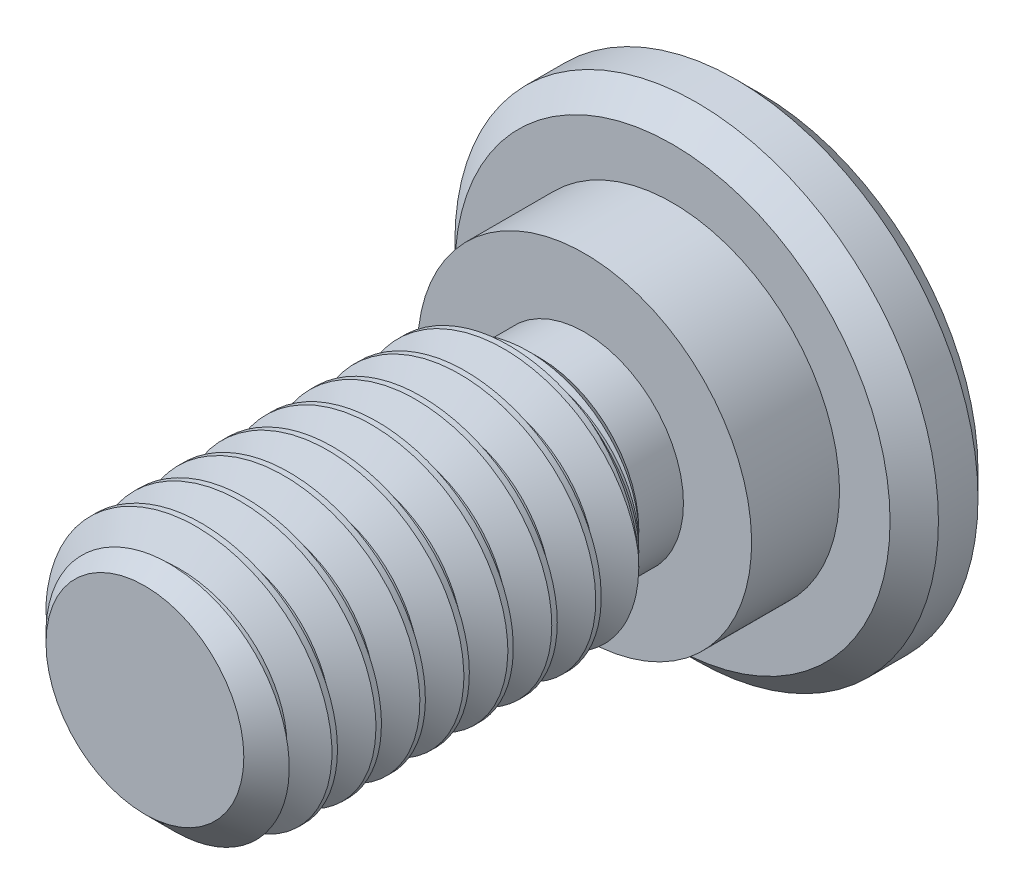
SolidWorks part; units mm, degrees
other "DetailItem1"
ref_plane "Front Plane" through (0, 0, 0) normal (0, 0, 1) x (1, 0, 0)
ref_plane "Top Plane" through (0, 0, 0) normal (0, 1, 0) x (1, 0, 0)
ref_plane "Right Plane" through (0, 0, 0) normal (1, 0, 0) x (0, 0, -1)
sketch "Sketch1" plane through (0, 0, 0) normal (1, 0, 0) x (0, 0, -1)
  line L0 (0, 0) -> (-6, 0) construction
  line L1 (0, 0) -> (1, 0) construction
  line L2 (1, 2.75) -> (1, -2.75) construction
  line L3 (-6, 1.5) -> (-6, -1.5) construction
  line L4 (0, 1.9) -> (0, -1.9) construction
  line L5 (-6, 1.5) -> (-5.5, 1.5) construction
  line L6 (1, 1) -> (1, -1) construction
  line L7 (0, 1.9) -> (-1, 1.9) construction
  line L8 (-1, 1.9) -> (-1, 1.125) construction
  line L9 (-1, 1.125) -> (-1.508, 1.125) construction
  line L10 (-1.508, 1.125) -> (-1.883, 1.5) construction
  point P2 (-4.25, -1.5)
  point P4 (-1, 0)
  point P8 (1, 0)
  point P11 (-6, 0)
  point P14 (0, 0)
  point P19 (1, 0)
  dimension "Thread Diameter" = 3
  dimension "Head Diameter" = 5.5
  dimension "Head Height" = 1
  dimension "Shoulder Diameter" = 3.8
  dimension "Shoulder Length" = 1
  dimension "Thread Pitch" = 0.5
  dimension "Drive Size" = 2
  dimension "D1" = 1.75
  dimension "D2" = 45
  dimension "Undercut Length" = 0.508
  dimension "D3" = 2.25
  dimension "Length" = 5
sketch "Sketch13" plane through (0, 0, 0) normal (1, 0, 0) x (0, 0, -1)
  line L0 (1, 2.75) -> (0, 2.75)
  line L1 (0, 2.75) -> (0, 1.9)
  line L3 (-6, 1.5) -> (-6, 0)
  line L4 (-6, 0) -> (1, 0)
  line L5 (1, 0) -> (1, 2.75)
  line L6 (-1.508, 1.125) -> (-1.883, 1.5) construction
  line L7 (-1, 1.125) -> (-1.508, 1.125) construction
  line L8 (-1, 1.9) -> (-1, 1.125) construction
  line L9 (0, 1.9) -> (-1, 1.9) construction
  line L10 (-1.508, 1.125) -> (-1.883, 1.5)
  line L11 (-1, 1.125) -> (-1.508, 1.125)
  line L12 (-1, 1.9) -> (-1, 1.125)
  line L13 (0, 1.9) -> (-1, 1.9)
  line L14 (-1.883, 1.5) -> (-6, 1.5)
revolve "Revolve1" add sketch "Sketch13" angle 360 about L4
sketch "Sketch2" plane through (0, 0, 6) normal (0, 0, 1) x (1, 0, 0)
  circle A2 centre (0, 0) radius 1.5
chamfer "Chamfer2" distance 0.375 angle 45 1 edges at (0, -1.5, 6)
sketch "Sketch3" plane through (0, 0, 0) normal (1, 0, 0) x (0, 0, -1)
  line L0 (-5.9687, 1.5541) -> (-6.4687, 1.5541) construction
  line L1 (-6.4687, 1.5541) -> (-6.2187, 1.1211) construction
  line L2 (-6.2187, 1.1211) -> (-5.9687, 1.5541) construction
  line L4 (-6, 1.5) -> (-6.4375, 1.5) construction
  line L5 (-6.2187, 1.5541) -> (-6.2187, 1.5) construction
  line L6 (-6.4531, 1.5271) -> (-5.9844, 1.5271)
  line L7 (-5.9844, 1.5271) -> (-6.4531, 1.5271) construction
  line L8 (-6.1875, 1.1752) -> (-6.25, 1.1752) construction
  line L9 (-6.2187, 1.1752) -> (-6.2187, 1.1211) construction
  line L10 (-5.9844, 1.5271) -> (-6.1875, 1.1752)
  line L11 (-6.1875, 1.1752) -> (-6.25, 1.1752)
  line L12 (-6.25, 1.1752) -> (-6.4531, 1.5271)
  point P16 (-6.2187, 1.5271)
  dimension "D1" = 0.5
  dimension "D2" = 0.0625
sketch "Sketch7" plane through (0, 0, -1) normal (0, 0, -1) x (-1, 0, 0)
  line L1 (0, 1.1547) -> (-1, 0.5774)
  line L2 (-1, 0.5774) -> (-1, -0.5774)
  line L3 (-1, -0.5774) -> (0, -1.1547)
  line L4 (0, -1.1547) -> (1, -0.5774)
  line L5 (1, -0.5774) -> (1, 0.5774)
  line L6 (1, 0.5774) -> (0, 1.1547)
  circle A0 centre (0, 0) radius 1 construction
extrude "Cut-Extrude1" cut sketch "Sketch7" against normal blind 1.5
chamfer "Chamfer1" distance 0.275 angle 45 2 edges at (0, -2.75, -1) (0, -2.75, 0)
sketch "Sketch8" plane through (0, 0, -1) normal (0, 0, -1) x (-1, 0, 0)
  circle A0 centre (0, 0) radius 1.1547
extrude "Cut-Extrude2" cut sketch "Sketch8" against normal through all draft 45
curve "Helix/Spiral1" pitch 0.5 height 4.9 radius 1.5 centre (0, 0, 6) axis (0, 0, -1) start towards (0, 1, 0) parameters "pitch"=0.5
sweep "Cut-Sweep1" cut profiles "Sketch3" path "Helix/Spiral1"
equation "\"D3@Helix/Spiral1\"=\"Length@Sketch1\"-.1"
equation "\"D1@Cut-Extrude1\" = \"Drive Size@Sketch1\" * .75"
equation "\"D1@Chamfer1\" = \"Head Diameter@Sketch1\" * .05"
equation "\"D1@Chamfer2\"=\"pitch@Helix/Spiral1\"*.750"
equation "\"D1@Sketch3\" = \"Thread Pitch@Sketch1\""
equation "\"D2@Sketch3\"=\"D1@Sketch3\"/ 1/8"
equation "\"pitch@Helix/Spiral1\" = \"Thread Pitch@Sketch1\""
equation "\"D1@Sketch1\" = \"Thread Pitch@Sketch1\" * 3.5"
equation "\"D3@Sketch1\"=\"Thread Diameter@Sketch1\"-(\"Thread Pitch@Sketch1\"*1.5)"
